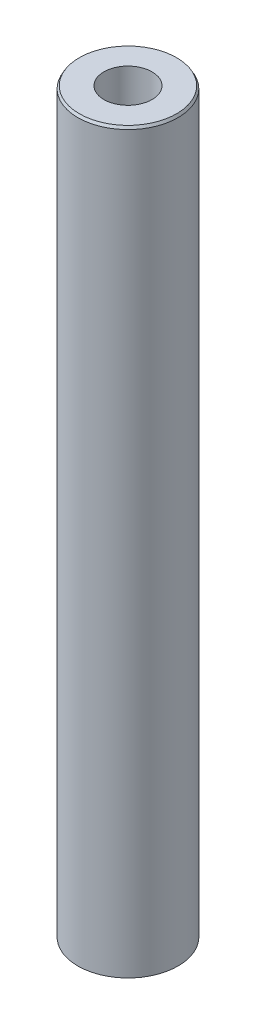
SolidWorks part; units mm, degrees
ref_plane "Front Plane" through (0, 0, 0) normal (0, 0, 1) x (1, 0, 0)
ref_plane "Top Plane" through (0, 0, 0) normal (0, 1, 0) x (1, 0, 0)
ref_plane "Right Plane" through (0, 0, 0) normal (1, 0, 0) x (0, 0, -1)
sketch "Sketch1" plane through (0, 0, 0) normal (0, 1, 0) x (1, 0, 0)
  circle A0 centre (0, 0) radius 30
  dimension "SHAFT_OD" = 60
extrude "Boss-Extrude1" add sketch "Sketch1" along normal blind 442.2219
sketch "Sketch2" plane through (0, 0, 0) normal (0, 1, 0) x (1, 0, 0)
  circle A0 centre (0, 0) radius 14.3999
  dimension "BORE_D" = 28.7998
extrude "Cut-Extrude1" cut sketch "Sketch2" along normal through all
chamfer "Chamfer1" distance 1.5603 angle 30 2 edges at (0, 442.2219, 30) (0, 0, 30) first distance on face at (0, 442.2219, 30) first distance on face at (0, 0, 14.3999)
